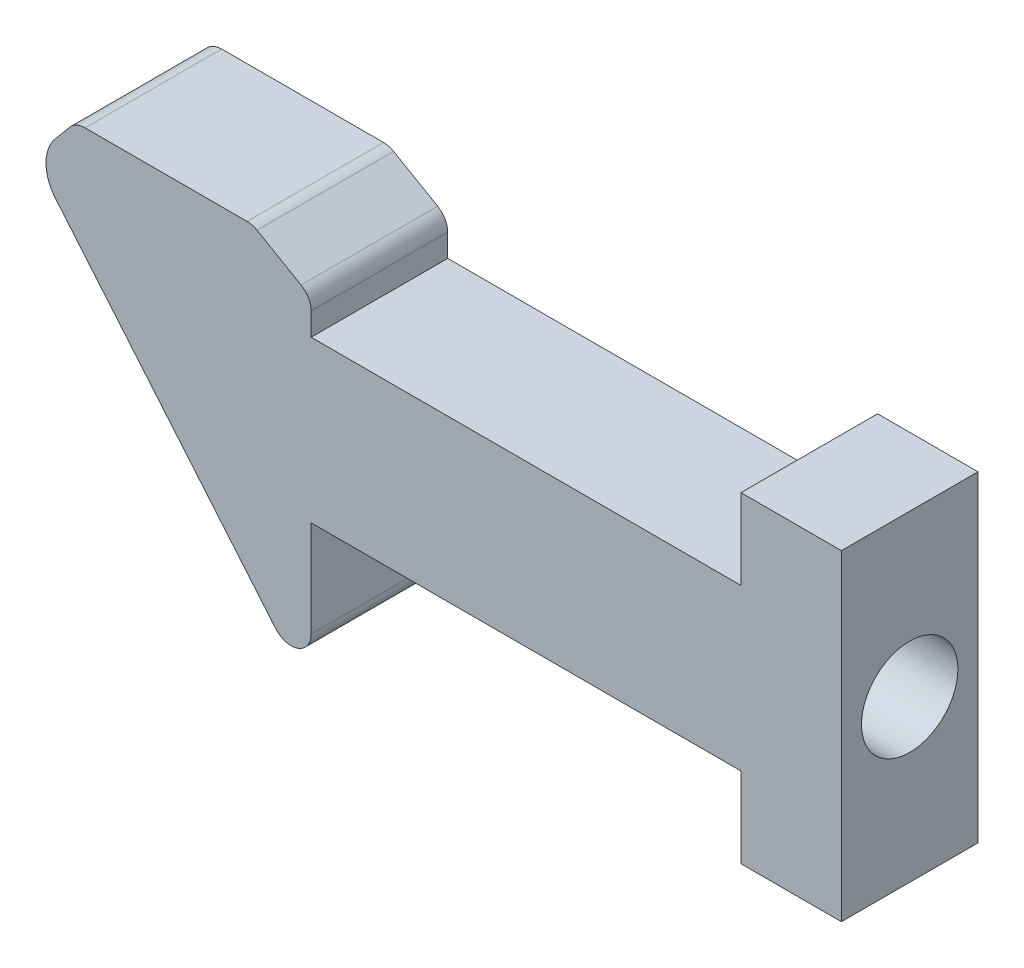
SolidWorks part; units mm, degrees
material "6061 Alloy"
ref_plane "Front Plane" through (0, 0, 0) normal (0, 0, 1) x (1, 0, 0)
ref_plane "Top Plane" through (0, 0, 0) normal (0, 1, 0) x (1, 0, 0)
ref_plane "Right Plane" through (0, 0, 0) normal (1, 0, 0) x (0, 0, -1)
sketch "Sketch2" plane through (0, 0, 0) normal (0, 0, 1) x (1, 0, 0)
  line L1 (-18.8283, 3.7) -> (-14.7964, 3.7)
  line L2 (55, 0) -> (-55, 0) construction
  line L6 (-19.566, 1.813) -> (-14.083, -4.7214)
  line L8 (-13.2, -4.4) -> (-13.2, -2)
  line L11 (-2.5, 2) -> (-2.5, 4)
  line L12 (-2.5, 4) -> (0, 4)
  line L13 (0, 4) -> (0, -4)
  line L14 (0, -4) -> (-2.5, -4)
  line L15 (-2.5, -4) -> (-2.5, -2)
  line L16 (-13.2, 2) -> (-2.5, 2)
  line L17 (-13.2, -2) -> (-2.5, -2)
  line L18 (-19.566, 3.0986) -> (-19.2113, 3.5214)
  line L19 (-13.2, 2) -> (-13.2, 2.567)
  line L20 (-13.45, 3) -> (-14.5464, 3.633)
  arc A1 (-14.083, -4.7214) -> (-13.2, -4.4) centre (-13.7, -4.4) ccw
  arc A3 (-19.566, 1.813) -> (-19.566, 3.0986) centre (-18.8, 2.4558) cw
  arc A4 (-18.8283, 3.7) -> (-19.2113, 3.5214) centre (-18.8283, 3.2) ccw
  arc A5 (-14.5464, 3.633) -> (-14.7964, 3.7) centre (-14.7964, 3.2) ccw
  arc A6 (-13.2, 2.567) -> (-13.45, 3) centre (-13.7, 2.567) ccw
  point P9 (0, 0)
  point P20 (-13.2, -5.7737)
  dimension "D1" = 1
  dimension "D9" = 30
  dimension "D4" = 0.5
  dimension "D12" = 0.5
  dimension "D6" = 0.5
  dimension "D15" = 0.5
  dimension "D2" = 2.5
  dimension "D3" = 13.2
  dimension "D5" = 2.4
  dimension "D7" = 8
  dimension "D8" = 4
  dimension "D10" = 1.2
  dimension "D11" = 5.1
  dimension "D13" = 40
  dimension "D14" = 40
  dimension "D16" = 1
extrude "Boss-Extrude3" add sketch "Sketch2" along normal mid plane 3.4
sketch "Sketch3" plane through (0, 0, 0) normal (1, 0, 0) x (0, 0, -1)
  line L0 (-1.7, 4) -> (1.7, 4) construction
  circle A0 centre (0, 0) radius 0.95
  point P7 (0, 4)
  dimension "D1" = 1.9
  dimension "D2" = 2
extrude "Cut-Extrude1" cut sketch "Sketch3" against normal blind 9.5
sketch "Sketch4" plane through (0, 0, 0) normal (1, 0, 0) x (0, 0, -1)
  circle A0 centre (0, 0) radius 1.2
  dimension "D1" = 2.4
extrude "Cut-Extrude2" cut sketch "Sketch4" against normal blind 2.8
